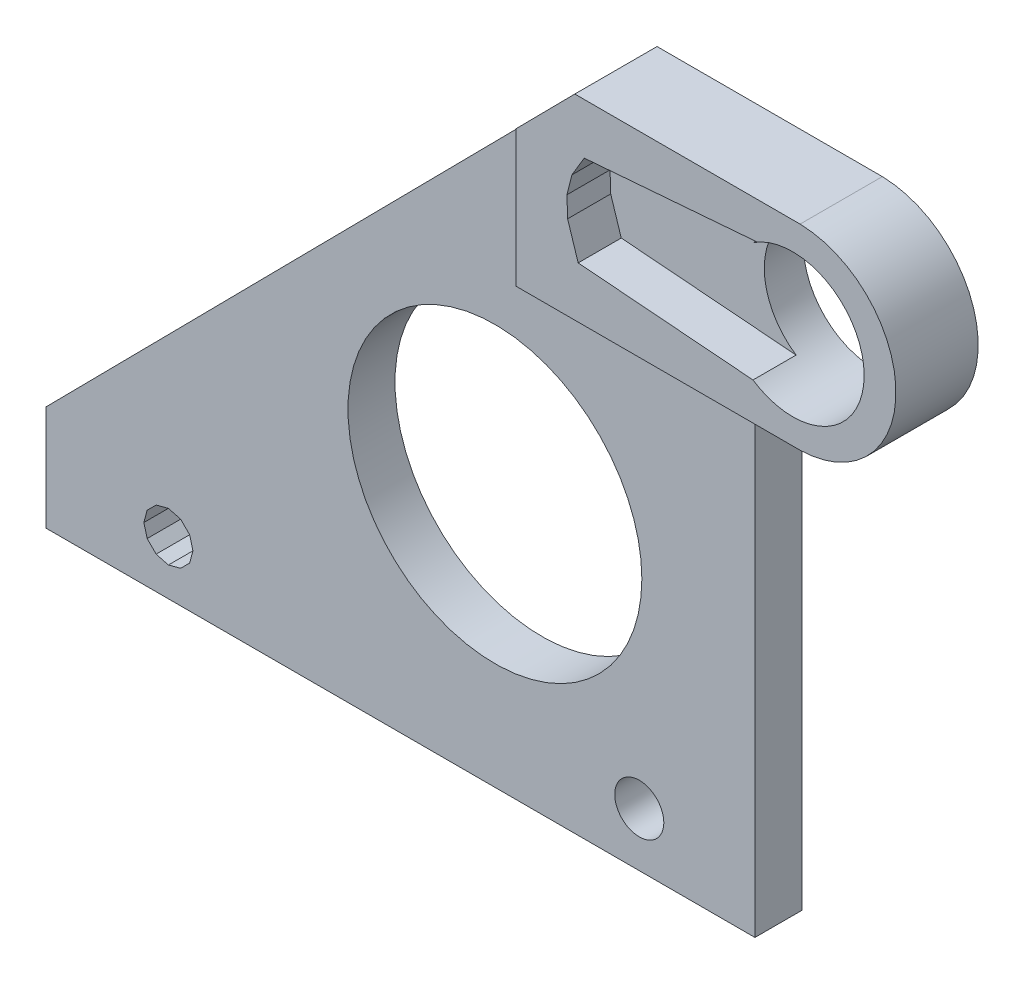
SolidWorks part; units mm, degrees
material "ABS"
ref_plane "Plan de face" through (0, 0, 0) normal (0, 0, 1) x (1, 0, 0)
ref_plane "Plan de dessus" through (0, 0, 0) normal (0, 1, 0) x (1, 0, 0)
ref_plane "Plan de droite" through (0, 0, 0) normal (1, 0, 0) x (0, 0, -1)
ref_plane "Plan1" through (0, 0, 4.2) normal (0, 0, 1) x (1, 0, 0)
sketch "Esquisse1" plane through (0, 0, 4.2) normal (0, 0, 1) x (1, 0, 0)
  line L18 (60.0015, 4.5) -> (46.9242, -8.7294)
  line L19 (46.9242, -8.7294) -> (36.198, -19.5803)
  line L20 (36.198, -19.5803) -> (31.2, -24.6364)
  line L21 (31.2, -24.6364) -> (71.5056, -24.6364)
  line L22 (71.5056, -24.6364) -> (71.5056, -5.5)
  line L34 (71.5056, 4.5) -> (60.0015, 4.5)
  arc A1 (71.5056, 4.5) -> (71.5056, -5.5) centre (71.3989, -0.5) cw
  circle A3 centre (71.1276, -0.5588) radius 3.65
extrude "Boss.-Extru.1" add sketch "Esquisse1" against normal blind 4.2
sketch "Esquisse2" plane through (0, 0, 4.2) normal (0, 0, 1) x (1, 0, 0)
  line L0 (59.602, -0.154) -> (59.635, -1.202)
  line L1 (59.635, -1.202) -> (60.1737, -2.8829)
  line L2 (60.1737, -2.8829) -> (69.2963, -3.6105)
  line L3 (69.2963, -3.6105) -> (68.506, -3.083) construction
  line L4 (68.506, -3.083) -> (67.715, -1.898) construction
  line L5 (67.715, -1.898) -> (67.436, -0.5) construction
  line L6 (67.436, -0.5) -> (67.715, 0.898) construction
  line L7 (67.715, 0.898) -> (68.506, 2.083) construction
  line L8 (68.506, 2.083) -> (69.2963, 2.6105) construction
  line L9 (69.2963, 2.6105) -> (60.4841, 1.9076)
  line L10 (60.4841, 1.9076) -> (59.856, 0.854)
  line L11 (59.856, 0.854) -> (59.602, -0.154)
  arc A0 (69.2963, 2.6105) -> (69.2963, -3.6105) centre (71.3268, -0.5) ccw
extrude "Enlèv. mat.-Extru.1" cut sketch "Esquisse2" against normal blind 2.2
sketch "Esquisse3" plane through (0, 0, 4.2) normal (0, 0, 1) x (1, 0, 0)
  line L0 (36.198, -19.5803) -> (31.2, -24.6364)
  line L1 (31.2, -24.6364) -> (71.5056, -24.6364)
  line L2 (71.5056, -24.6364) -> (71.5056, -5.5)
  line L3 (71.5056, -5.5) -> (46.9242, -8.7294)
  line L4 (46.9242, -8.7294) -> (36.198, -19.5803)
extrude "Enlèv. mat.-Extru.2" cut sketch "Esquisse3" against normal blind 1.8
sketch "Esquisse4" plane through (0, 0, 4.2) normal (0, 0, 1) x (1, 0, 0)
  line L0 (57, -7.4057) -> (57, 1.4636)
  line L1 (57, 1.4636) -> (46.9242, -8.7294)
  line L2 (46.9242, -8.7294) -> (57, -7.4057)
extrude "Enlèv. mat.-Extru.3" cut sketch "Esquisse4" against normal blind 1.8
sketch "Esquisse5" plane through (0, 0, 4.2) normal (0, 0, 1) x (1, 0, 0)
  line L0 (71.5056, -5.5) -> (57, -5.5)
  line L1 (57, -5.5) -> (57, -7.4057)
  line L2 (57, -7.4057) -> (71.5056, -5.5)
extrude "Enlèv. mat.-Extru.4" cut sketch "Esquisse5" against normal blind 1.8
sketch "Esquisse6" plane through (71.5056, 0, 0) normal (1, 0, 0) x (0, 0, -1)
  line L0 (-2.4, -5.5) -> (-2.4, -24.6364)
  line L1 (-2.4, -24.6364) -> (0, -24.6364)
  line L2 (0, -24.6364) -> (0, -5.5)
  line L3 (0, -5.5) -> (-2.4, -5.5)
extrude "Enlèv. mat.-Extru.5" cut sketch "Esquisse6" against normal blind 4.1056
sketch "Esquisse7" plane through (0, -24.6364, 0) normal (0, -1, 0) x (1, 0, 0)
  line L0 (31.2, 2.4) -> (67.4, 2.4)
  line L1 (67.4, 2.4) -> (67.4, 0)
  line L2 (67.4, 0) -> (31.2, 0)
  line L3 (31.2, 0) -> (31.2, 2.4)
extrude "Boss.-Extru.2" add sketch "Esquisse7" along normal blind 5.3636
sketch "Esquisse8" plane through (0, 0, 2.4) normal (0, 0, 1) x (1, 0, 0)
  line L0 (59.4508, -22.3329) -> (60.3838, -21.1959) construction
  line L1 (60.3838, -21.1959) -> (61.0768, -19.8989) construction
  line L2 (61.0768, -19.8989) -> (61.5038, -18.4919) construction
  line L3 (61.5038, -18.4919) -> (61.6488, -17.0279) construction
  line L4 (61.6488, -17.0279) -> (61.5063, -15.5895) construction
  line L5 (61.5063, -15.5895) -> (61.0793, -14.1825) construction
  line L6 (61.0793, -14.1825) -> (60.3863, -12.8855) construction
  line L7 (60.3863, -12.8855) -> (59.4533, -11.7485) construction
  line L8 (59.4533, -11.7485) -> (58.268, -10.762) construction
  line L9 (58.268, -10.762) -> (56.971, -10.069) construction
  line L10 (56.971, -10.069) -> (55.564, -9.642) construction
  line L11 (55.564, -9.642) -> (54.1, -9.498) construction
  line L12 (54.1, -9.498) -> (52.636, -9.642) construction
  line L13 (52.636, -9.642) -> (51.229, -10.069) construction
  line L14 (51.229, -10.069) -> (49.932, -10.762) construction
  line L15 (49.932, -10.762) -> (49.3636, -11.2284) construction
  line L16 (49.3636, -11.2284) -> (48.4306, -12.3654) construction
  line L17 (48.4306, -12.3654) -> (47.7376, -13.6624) construction
  line L18 (47.7376, -13.6624) -> (47.3106, -15.0694) construction
  line L19 (47.3106, -15.0694) -> (47.1666, -16.5334) construction
  line L20 (47.1666, -16.5334) -> (47.3106, -17.9974) construction
  line L21 (47.3106, -17.9974) -> (47.7376, -19.4044) construction
  line L22 (47.7376, -19.4044) -> (48.4306, -20.7014) construction
  line L23 (48.4306, -20.7014) -> (49.3636, -21.8384) construction
  line L24 (49.3636, -21.8384) -> (50.5006, -22.7714) construction
  line L25 (50.5006, -22.7714) -> (51.7976, -23.4644) construction
  line L26 (51.7976, -23.4644) -> (53.2046, -23.8914) construction
  line L27 (53.2046, -23.8914) -> (54.1458, -24.5309) construction
  line L28 (54.1458, -24.5309) -> (55.6098, -24.3859) construction
  line L29 (55.6098, -24.3859) -> (57.0168, -23.9589) construction
  line L30 (57.0168, -23.9589) -> (58.3138, -23.2659) construction
  line L31 (58.3138, -23.2659) -> (59.4508, -22.3329) construction
  circle A0 centre (54.1229, -17.0283) radius 7.5027
extrude "Enlèv. mat.-Extru.6" cut sketch "Esquisse8" against normal through all
sketch "Esquisse9" plane through (0, 0, 2.4) normal (0, 0, 1) x (1, 0, 0)
  line L0 (60.2839, -26.9281) -> (60.198, -27.25) construction
  line L1 (60.198, -27.25) -> (60.365, -27.876) construction
  line L2 (60.365, -27.876) -> (60.824, -28.335) construction
  line L3 (60.824, -28.335) -> (61.45, -28.503) construction
  line L4 (61.45, -28.503) -> (62.076, -28.335) construction
  line L5 (62.076, -28.335) -> (62.535, -27.876) construction
  line L6 (62.535, -27.876) -> (62.703, -27.25) construction
  line L7 (62.703, -27.25) -> (62.5902, -26.6441) construction
  line L8 (62.5902, -26.6441) -> (61.9949, -26.4691) construction
  line L9 (61.9949, -26.4691) -> (61.3689, -26.3021) construction
  line L10 (61.3689, -26.3021) -> (60.7429, -26.4691) construction
  line L11 (60.7429, -26.4691) -> (60.2839, -26.9281) construction
  circle A0 centre (61.4943, -27.251) radius 1.2528
extrude "Enlèv. mat.-Extru.7" cut sketch "Esquisse9" against normal through all
sketch "Esquisse10" plane through (0, 0, 0) normal (0, 0, -1) x (-1, 0, 0)
  line L0 (-38.076, -26.165) -> (-38.535, -26.624)
  line L1 (-38.535, -26.624) -> (-38.703, -27.25)
  line L2 (-38.703, -27.25) -> (-38.535, -27.876)
  line L3 (-38.535, -27.876) -> (-38.076, -28.335)
  line L4 (-38.076, -28.335) -> (-37.45, -28.503)
  line L5 (-37.45, -28.503) -> (-36.824, -28.335)
  line L6 (-36.824, -28.335) -> (-36.365, -27.876)
  line L7 (-36.365, -27.876) -> (-36.198, -27.25)
  line L8 (-36.198, -27.25) -> (-36.365, -26.624)
  line L9 (-36.365, -26.624) -> (-36.824, -26.165)
  line L10 (-36.824, -26.165) -> (-37.45, -25.998)
  line L11 (-37.45, -25.998) -> (-38.076, -26.165)
extrude "Enlèv. mat.-Extru.8" cut sketch "Esquisse10" against normal through all
